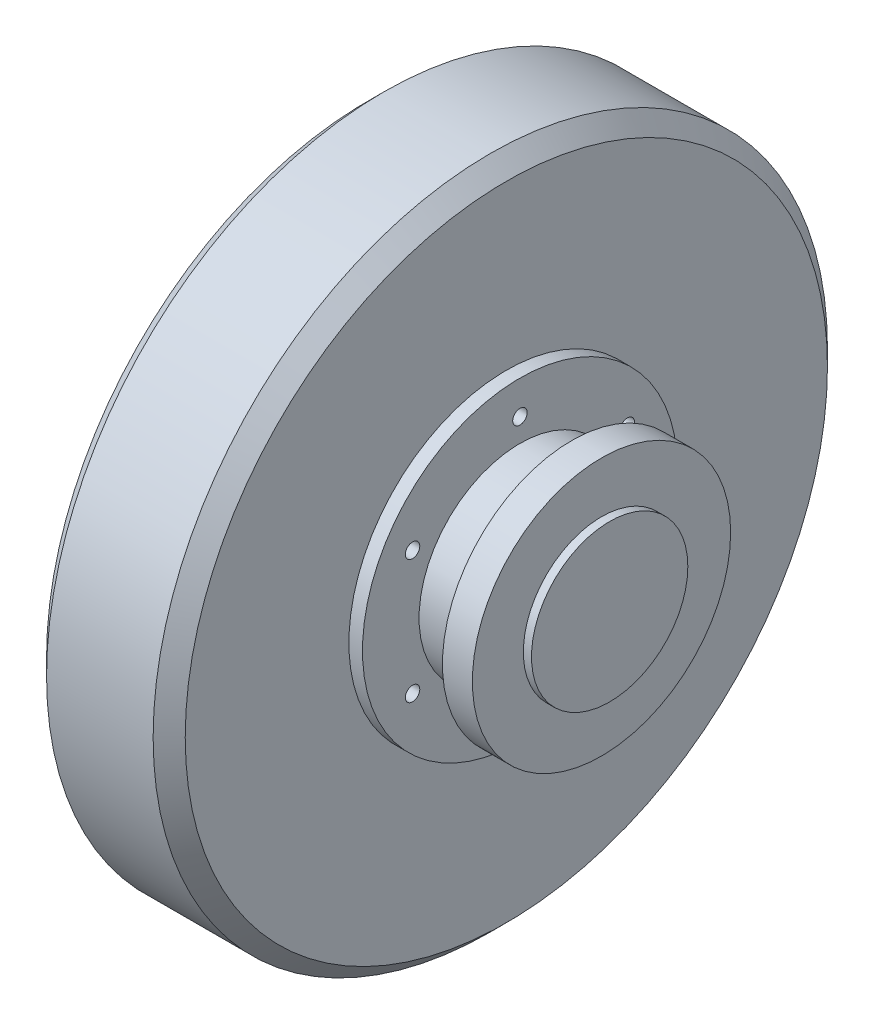
SolidWorks part; units mm, degrees
ref_plane "Front Plane" through (0, 0, 0) normal (1, 0, 0) x (0, 1, 0)
ref_plane "Top Plane" through (0, 0, 0) normal (0, 0, 1) x (0, 1, 0)
ref_plane "Right Plane" through (0, 0, 0) normal (0, 1, 0) x (-1, 0, 0)
sketch "Sketch1" plane through (0, 0, 0) normal (0, 1, 0) x (-1, 0, 0)
  line L0 (0, 73.5501) -> (6.35, 73.5501)
  line L1 (0, 0) -> (71.12, 0)
  line L2 (0, 0) -> (0, 157.48)
  line L3 (0, 157.48) -> (71.12, 157.48)
  line L4 (71.12, 0) -> (71.12, 157.48)
  line L5 (6.35, 73.5501) -> (6.35, 149.987)
  line L6 (6.35, 149.987) -> (13.843, 157.48)
  line L7 (63.627, 157.48) -> (71.12, 149.987)
  line L8 (-24.13, 60.325) -> (-24.13, 36.5125)
  line L9 (0, 0) -> (-20.32, 0)
  line L10 (0, 0) -> (0, 47.117)
  line L11 (0, 47.117) -> (-20.32, 47.117)
  line L12 (-20.32, 0) -> (-20.32, 47.117)
  line L13 (71.12, 0) -> (83.82, 0)
  line L14 (71.12, 0) -> (71.12, 14.9987)
  line L15 (71.12, 14.9987) -> (83.82, 14.9987)
  line L16 (83.82, 0) -> (83.82, 14.9987)
  line L17 (83.82, 0) -> (90.17, 0)
  line L18 (83.82, 0) -> (83.82, 24.13)
  line L19 (83.82, 24.13) -> (90.17, 24.13)
  line L20 (90.17, 0) -> (90.17, 24.13)
  line L21 (-20.32, 0) -> (-41.91, 0)
  line L22 (-20.32, 0) -> (-20.32, 36.5125)
  line L23 (-20.32, 36.5125) -> (-41.91, 36.5125)
  line L24 (-41.91, 0) -> (-41.91, 36.5125)
  line L25 (-24.13, 36.5125) -> (-38.1, 36.5125)
  line L26 (-38.1, 36.5125) -> (-38.1, 60.325)
  line L27 (-38.1, 60.325) -> (-24.13, 60.325)
  dimension "D1" = 157.48
  dimension "D2" = 71.12
  dimension "D3" = 12.7
  dimension "D4" = 6.35
  dimension "D5" = 14.9987
  dimension "D6" = 24.13
  dimension "D7" = 20.32
  dimension "D8" = 45
  dimension "D9" = 45
  dimension "D10" = 6.35
  dimension "D11" = 47.117
  dimension "D13" = 36.5125
  dimension "D14" = 132.08
  dimension "D12" = 49.784
  dimension "D15" = 24.13
  dimension "D16" = 60.325
  dimension "D17" = 13.97
  dimension "D18" = 36.5125
revolve "Revolve1" add sketch "Sketch1" angle 360 about L1 region at (-37.1698, 0, 76.4895) region at (10.16, 0, 23.5585) region at (-77.47, 0, 7.4993) region at (31.115, 0, 18.2562) region at (-86.995, 0, 12.065)
revolve "Revolve2" add sketch "Sketch1<3>" angle 360 about L1 region at (31.115, 0, 48.4188)
sketch "Sketch1<3>" plane through (0, 0, 0) normal (0, 1, 0) x (-1, 0, 0) same geometry as "Sketch1"
sketch "Sketch2" plane through (-71.12, 0, 0) normal (-1, 0, 0) x (0, -1, 0)
  line L1 (0, -38.1) -> (36.2353, -11.7735)
  line L2 (36.2353, -11.7735) -> (22.3946, 30.8235)
  line L3 (22.3946, 30.8235) -> (-22.3946, 30.8235)
  line L4 (-22.3946, 30.8235) -> (-36.2353, -11.7735)
  line L5 (-36.2353, -11.7735) -> (0, -38.1)
  circle A0 centre (0, 0) radius 38.1
  circle A1 centre (0, 0) radius 149.987
  circle A2 centre (0, 0) radius 149.987
  circle A3 centre (0, 0) radius 30.8235 construction
  dimension "D2" = 76.2
  dimension "D1" = 0
sketch "Sketch3" plane through (-71.12, 0, 0) normal (-1, 0, 0) x (0, -1, 0)
  circle A0 centre (-22.3946, 30.8235) radius 3.3734
  circle A1 centre (22.3946, 30.8235) radius 3.3734
  circle A2 centre (36.2353, -11.7735) radius 3.3734
  circle A3 centre (0, -38.1) radius 3.3734
  circle A4 centre (-36.2353, -11.7735) radius 3.3734
  point P0 (-36.2353, -11.7735)
  point P2 (0, -38.1)
  point P4 (36.2353, -11.7735)
  point P6 (22.3946, 30.8235)
  point P8 (-22.3946, 30.8235)
  dimension "D1" = 6.7469
extrude "Cut-Extrude1" cut sketch "Sketch3" against normal blind 11.43
sketch "Sketch4" plane through (0, 0, 0) normal (1, 0, 0) x (0, 1, 0)
  line L0 (28.956, -50.1533) -> (57.912, 0)
  line L1 (57.912, 0) -> (28.956, 50.1533)
  line L2 (28.956, 50.1533) -> (-28.956, 50.1533)
  line L3 (-28.956, 50.1533) -> (-57.912, 0)
  line L4 (-57.912, 0) -> (-28.956, -50.1533)
  line L5 (-28.956, -50.1533) -> (28.956, -50.1533)
  circle A0 centre (0, 0) radius 50.1533 construction
  circle A1 centre (0, 0) radius 73.5501
  circle A2 centre (0, 0) radius 73.5501
  circle A3 centre (28.956, 50.1533) radius 3.3734
  dimension "D3" = 6.7469
  dimension "D2" = 115.824
  dimension "D1" = 0
sketch "Sketch5" plane through (0, 0, 0) normal (1, 0, 0) x (0, 1, 0)
  circle A0 centre (28.956, 50.1533) radius 3.3734 construction
  circle A1 centre (28.956, 50.1533) radius 3.3734
  circle A2 centre (-28.956, 50.1533) radius 3.3734
  circle A3 centre (-57.912, 0) radius 3.3734
  circle A4 centre (-28.956, -50.1533) radius 3.3734
  circle A5 centre (28.956, -50.1533) radius 3.3734
  circle A6 centre (57.912, 0) radius 3.3734
  point P0 (28.956, -50.1533)
  point P2 (57.912, 0)
  point P4 (28.956, 50.1533)
  point P9 (-28.956, -50.1533)
  point P11 (-57.912, 0)
  point P13 (-28.956, 50.1533)
extrude "Cut-Extrude2" cut sketch "Sketch5" against normal blind 12.7
equation "\"D9@Sketch1\"=\"D8@Sketch1\""
